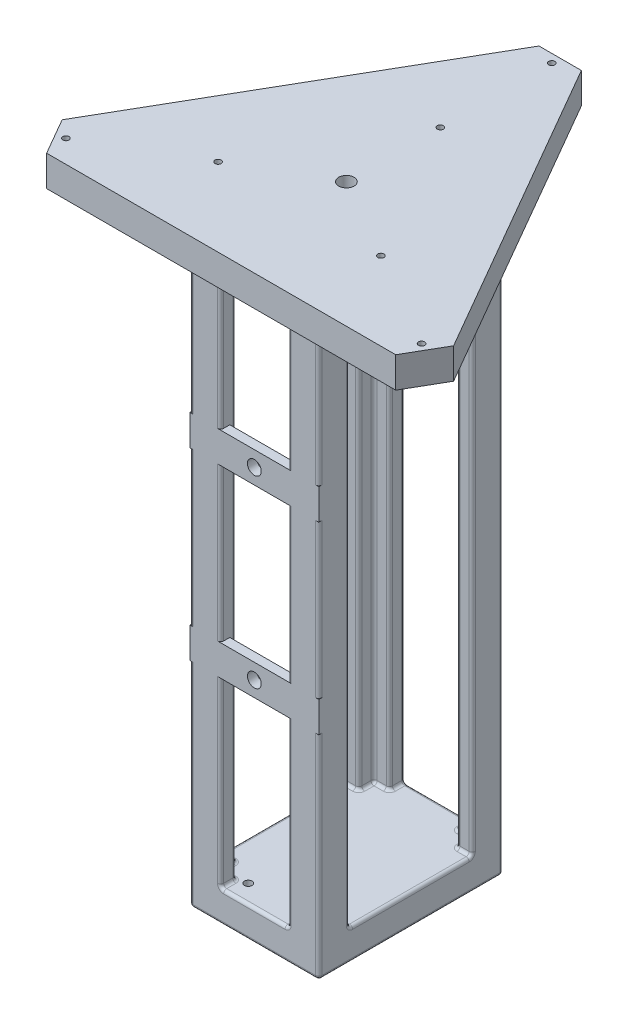
SolidWorks part; units mm, degrees
material "AISI 1035 Acier (SS)"
ref_plane "Plan de face" through (0, 0, 0) normal (0, 0, 1) x (1, 0, 0)
ref_plane "Plan de dessus" through (0, 0, 0) normal (0, 1, 0) x (1, 0, 0)
ref_plane "Plan de droite" through (0, 0, 0) normal (1, 0, 0) x (0, 0, -1)
sketch "Esquisse1" plane through (0, 0, 0) normal (0, 1, 0) x (1, 0, 0)
  line L29 (-6.9, 69.6591) -> (6.9, 69.6591)
  line L30 (63.7765, -28.854) -> (56.8765, -40.8051)
  line L31 (-56.8765, -40.8051) -> (-63.7765, -28.854)
  line L32 (-6.9, 69.6591) -> (-63.7765, -28.854)
  line L33 (-56.8765, -40.8051) -> (56.8765, -40.8051)
  line L34 (63.7765, -28.854) -> (6.9, 69.6591)
  circle A7 centre (0, 0) radius 2.5
  point P17 (0, 0)
  dimension "D1" = 13.8
  dimension "D4" = 13.8
  dimension "D5" = 70
  dimension "D6" = 70
  dimension "D3" = 70
  dimension "D9" = 5
  dimension "D2" = 13.8
  dimension "D7" = 60
  dimension "D8" = 60
  dimension "D10" = 70
  dimension "D11" = 70
extrude "Boss.-Extru.1" add sketch "Esquisse1" along normal mid plane 10
sketch "Esquisse3" plane through (0, -5, 0) normal (0, -1, 0) x (1, 0, 0)
  line L68 (21, 30) -> (11, 30)
  line L69 (21, -30) -> (-21, -30) construction
  line L70 (21, -30) -> (21, 30) construction
  line L71 (21, 30) -> (-21, 30) construction
  line L72 (-21, -30) -> (-21, 30) construction
  line L73 (21, -20) -> (16, -20)
  line L74 (16, -20) -> (16, -25)
  line L75 (11, 30) -> (11, 25)
  line L76 (11, 25) -> (16, 25)
  line L77 (16, 25) -> (16, 20)
  line L78 (16, 20) -> (21, 20)
  line L79 (21, 20) -> (21, 30)
  line L80 (21, -30) -> (21, -20)
  line L81 (16, -25) -> (11, -25)
  line L82 (11, -25) -> (11, -30)
  line L83 (-21, -30) -> (-21, -20)
  line L84 (-21, -20) -> (-16, -20)
  line L85 (-16, -20) -> (-16, -25)
  line L86 (-16, -25) -> (-11, -25)
  line L87 (-11, -25) -> (-11, -30)
  line L88 (-11, -30) -> (-21, -30)
  line L89 (-21, 30) -> (-21, 20)
  line L90 (-21, 20) -> (-16, 20)
  line L91 (-16, 20) -> (-16, 25)
  line L92 (-16, 25) -> (-11, 25)
  line L93 (-11, 25) -> (-11, 30)
  line L94 (-11, 30) -> (-21, 30)
  line L95 (11, -30) -> (21, -30)
  point P0 (0, 0)
  dimension "D1" = 42
  dimension "D2" = 60
  dimension "D3" = 10
  dimension "D4" = 10
  dimension "D5" = 5
  dimension "D6" = 5
  dimension "D7" = 25
  dimension "D8" = 5
  dimension "D9" = 5
  dimension "D10" = 5
  dimension "D11" = 10
  dimension "D12" = 5
  dimension "D13" = 5
  dimension "D14" = 5
  dimension "D15" = 10
  dimension "D16" = 16
extrude "Boss.-Extru.2" add sketch "Esquisse3" along normal blind 180
sketch "Esquisse7" plane through (0, -185, 0) normal (0, -1, 0) x (1, 0, 0)
  line L12 (21, -30) -> (-21, 30) construction
  line L13 (21, 30) -> (-21, -30) construction
  line L15 (21, -30) -> (-21, -30)
  line L16 (21, -30) -> (21, 30)
  line L17 (21, 30) -> (-21, 30)
  line L18 (-21, -30) -> (-21, 30)
  line L19 (21, -30) -> (-21, 30) construction
  line L20 (21, 30) -> (-21, -30) construction
  point P0 (0, 0)
  point P9 (0, 0)
  dimension "D1" = 42
  dimension "D2" = 60
extrude "Boss.-Extru.3" add sketch "Esquisse7" along normal blind 10
fillet "Congé3" radius 1 72 edges at (-18.5, -185, 20) (-18.5, -5, 20) (-16, -95, 20) (-16, -185, 22.5) (-16, -5, 22.5) (-16, -95, 25) (-13.5, -185, 25) (-13.5, -5, 25) (-11, -95, 25) (-11, -185, 27.5) (-11, -5, 27.5) (18.5, -185, -20) (18.5, -5, -20) (16, -95, -20) (16, -185, -22.5) (16, -5, -22.5) (16, -95, -25) (13.5, -185, -25) (13.5, -5, -25) (11, -95, -25) (11, -185, -27.5) (11, -5, -27.5) (11, -185, 27.5) (11, -5, 27.5) (11, -95, 25) (13.5, -185, 25) (13.5, -5, 25) (16, -95, 25) (16, -185, 22.5) (16, -5, 22.5) (16, -95, 20) (18.5, -185, 20) (18.5, -5, 20) (-11, -185, -27.5) (-11, -5, -27.5) (-11, -95, -25) (-13.5, -185, -25) (-13.5, -5, -25) (-16, -95, -25) (-16, -185, -22.5) (-16, -5, -22.5) (-16, -95, -20) (-18.5, -185, -20) (-18.5, -5, -20) (21, -5, 25) (21, -95, 20) (21, -95, -20) (21, -5, -25) (11, -95, -30) (-11, -95, -30) (-16, -5, -30) (21, -100, -30) (16, -5, -30) (-21, -100, -30) (-21, -5, -25) (-21, -95, -20) (-21, -95, 20) (-21, -5, 25) (-11, -95, 30) (11, -95, 30) (16, -5, 30) (21, -100, 30) (-21, -100, 30) (-16, -5, 30) (21, -195, 0) (21, -185, 0) (0, -185, -30) (0, -195, -30) (-21, -195, 0) (-21, -185, 0) (0, -185, 30) (0, -195, 30)
sketch "Esquisse8" plane through (0, -195, 0) normal (0, -1, 0) x (1, 0, 0)
  line L1 (0, -55) -> (0, 55) construction
  line L3 (20, 29) -> (-20, 29) construction
  circle A0 centre (8, 24) radius 1.25
  circle A1 centre (-8, 24) radius 1.25
  dimension "D2" = 2.5
  dimension "D1" = 8
  dimension "D3" = 5
extrude "Enlèv. mat.-Extru.4" cut sketch "Esquisse8" against normal up to next
sketch "Esquisse12" plane through (0, 0, 30) normal (0, 0, 1) x (1, 0, 0)
  line L0 (-21, -55.62) -> (21, -55.62)
  line L1 (-21, -55.62) -> (-21, -65.62)
  line L2 (-21, -65.62) -> (21, -65.62)
  line L3 (21, -55.62) -> (21, -65.62)
  line L4 (-21, -115.62) -> (21, -115.62)
  line L5 (-21, -115.62) -> (-21, -125.62)
  line L6 (-21, -125.62) -> (21, -125.62)
  line L7 (21, -115.62) -> (21, -125.62)
  line L8 (21, -6) -> (21, -194) construction
  line L9 (-21, -194) -> (-21, -6) construction
  line L10 (10, -186) -> (-10, -186) construction
  circle A0 centre (0, -60.62) radius 2.25
  circle A1 centre (0, -120.62) radius 2.25
  point P4 (21, -60.62)
  point P9 (21, -120.62)
  dimension "D6" = 4.5
  dimension "D7" = 4.5
  dimension "D1" = 10
  dimension "D2" = 10
  dimension "D3" = 60
  dimension "D4" = 125.38
  dimension "D5" = 5
  dimension "D8" = 5
extrude "Boss.-Extru.5" add sketch "Esquisse12" against normal blind 3
sketch "Esquisse14" plane through (0, 5, 0) normal (0, 1, 0) x (1, 0, 0)
  line L0 (-60.3265, -34.8295) -> (0, 0) construction
  line L1 (-63.7765, -28.854) -> (-56.8765, -40.8051) construction
  circle A0 centre (-57.945, -33.4545) radius 1
  circle A1 centre (-26.5083, -15.3045) radius 1
  dimension "D1" = 2
  dimension "D4" = 2
  dimension "D2" = 2.75
  dimension "D3" = 39.05
extrude "Enlèv. mat.-Extru.5" cut sketch "Esquisse14" against normal through all
pattern_circular "Répétition circulaire1" count 3 over 360 about axis through (0, 5, 0) along (0, -1, 0) of "Enlèv. mat.-Extru.5" reverse direction yes
